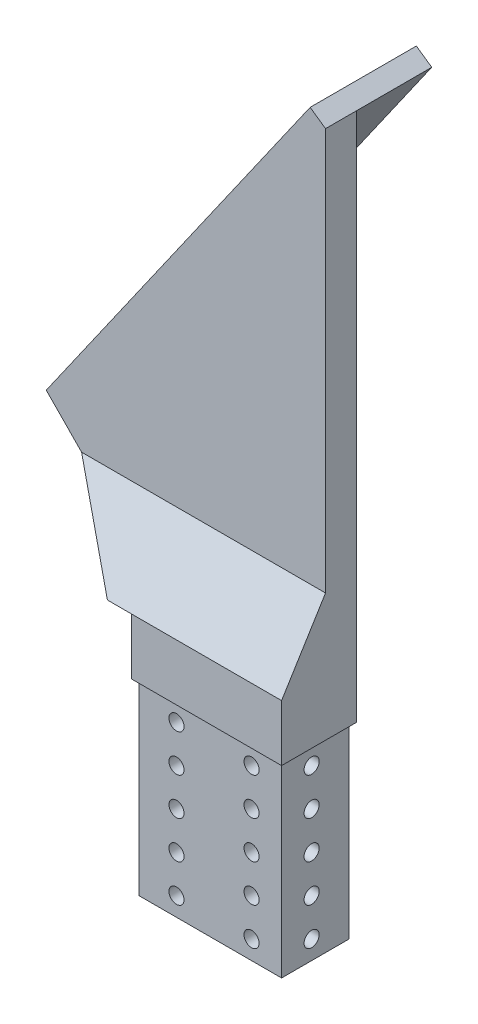
SolidWorks part; units mm, degrees
ref_plane "Front Plane" through (0, 0, 0) normal (0, 0, 1) x (1, 0, 0)
ref_plane "Top Plane" through (0, 0, 0) normal (0, 1, 0) x (1, 0, 0)
ref_plane "Right Plane" through (0, 0, 0) normal (1, 0, 0) x (0, 0, -1)
sketch "Sketch1" plane through (0, 0, 0) normal (0, 0, 1) x (1, 0, 0)
  line L0 (50.8, 82.55) -> (152.4, 82.55)
  line L1 (0, 0) -> (50.8, 0)
  line L2 (0, 0) -> (0, 82.55)
  line L4 (50.8, 0) -> (50.8, 82.55)
  line L5 (-101.6, 82.55) -> (0, 82.55)
  line L6 (-101.6, 82.55) -> (-101.6, 254)
  line L7 (-101.6, 254) -> (152.4, 254)
  line L8 (152.4, 82.55) -> (152.4, 254)
  dimension "D1" = 50.8
  dimension "D2" = 82.55
  dimension "D3" = 254
  dimension "D4" = 171.45
extrude "Boss-Extrude1" add sketch "Sketch1" along normal blind 25.4
sketch "Sketch3" plane through (0, 0, 25.4) normal (0, 0, 1) x (1, 0, 0)
  line L0 (50.8, 0) -> (50.8, 82.55) construction
  line L1 (0, 0) -> (50.8, 0)
  line L2 (0, 0) -> (0, 63.5)
  line L3 (0, 63.5) -> (50.8, 63.5)
  line L4 (50.8, 0) -> (50.8, 63.5)
  dimension "D1" = 63.5
sketch "Sketch4" plane through (0, 0, 0) normal (-1, 0, 0) x (0, 0, 1)
  line L0 (25.4, 0) -> (25.4, 63.5) construction
  line L1 (0, 0) -> (25.4, 0)
  line L2 (0, 0) -> (0, 63.5)
  line L3 (0, 63.5) -> (25.4, 63.5)
  line L4 (25.4, 0) -> (25.4, 63.5)
  dimension "D1" = 63.5
sketch "Sketch5" plane through (0, 0, 0) normal (0, 0, -1) x (-1, 0, 0)
  line L1 (0, 0) -> (-50.8, 0)
  line L2 (0, 0) -> (0, 63.5)
  line L3 (0, 63.5) -> (-50.8, 63.5)
  line L4 (-50.8, 0) -> (-50.8, 63.5)
sketch "Sketch6" plane through (50.8, 0, 0) normal (1, 0, 0) x (0, 0, -1)
  line L1 (0, 0) -> (-25.4, 0)
  line L2 (0, 0) -> (0, 63.5)
  line L3 (0, 63.5) -> (-25.4, 63.5)
  line L4 (-25.4, 0) -> (-25.4, 63.5)
extrude "Cut-Extrude1" cut sketch "Sketch3" against normal blind 1.27
extrude "Cut-Extrude2" cut sketch "Sketch4" against normal blind 1.27
extrude "Cut-Extrude3" cut sketch "Sketch5" against normal blind 1.27
extrude "Cut-Extrude4" cut sketch "Sketch6" against normal blind 1.27
sketch "Sketch7" plane through (0, 0, 25.4) normal (0, 0, 1) x (1, 0, 0)
  line L0 (50.8, 82.55) -> (50.8, 254)
  line L4 (152.4, 254) -> (-101.6, 254) construction
  line L5 (50.8, 82.55) -> (152.4, 82.55)
  line L6 (152.4, 82.55) -> (152.4, 254)
  line L7 (152.4, 254) -> (50.8, 254)
extrude "Cut-Extrude5" cut sketch "Sketch7" against normal through all
sketch "Sketch9" plane through (0, 0, 25.4) normal (0, 0, 1) x (1, 0, 0)
  line L0 (34.6576, 254) -> (50.8, 254)
  line L1 (50.8, 254) -> (-101.6, 254) construction
  line L2 (50.8, 254) -> (50.8, 242.697)
  line L3 (50.8, 242.697) -> (34.6576, 254)
  line L4 (50.8, 63.5) -> (50.8, 254) construction
  dimension "D1" = 11.303
  dimension "D2" = 35
extrude "Cut-Extrude7" cut sketch "Sketch9" against normal through all
sketch "Sketch8" plane through (0, 0, 25.4) normal (0, 0, 1) x (1, 0, 0)
  line L2 (34.6576, 254) -> (-101.6, 254) construction
  line L12 (34.6576, 254) -> (-101.6, 59.4039)
  line L13 (-101.6, 59.4039) -> (-101.6, 254)
  line L14 (-101.6, 254) -> (34.6576, 254)
  dimension "D1" = 55
extrude "Cut-Extrude6" cut sketch "Sketch8" against normal through all
sketch "Sketch10" plane through (0, 0, 25.4) normal (0, 0, 1) x (1, 0, 0)
  line L0 (34.6576, 254) -> (45.5977, 246.3397)
  line L1 (34.6576, 254) -> (50.8, 242.697) construction
  line L2 (45.5977, 246.3397) -> (-84.0298, 61.2124)
  line L4 (-84.0298, 61.2124) -> (-94.9699, 68.8727)
  line L5 (-94.9699, 68.8727) -> (34.6576, 254)
  line L6 (-85.3929, 82.55) -> (34.6576, 254) construction
  dimension "D1" = 13.3553
  dimension "D2" = 13.3553
extrude "Cut-Extrude8" cut sketch "Sketch10" against normal through all
sketch "Sketch11" plane through (0, 0, 24.13) normal (0, 0, 1) x (1, 0, 0)
  line L0 (1.27, 63.5) -> (1.27, 0) construction
  line L1 (50.8, 63.5) -> (0, 63.5) construction
  line L2 (49.53, 63.5) -> (1.27, 63.5) construction
  circle A0 centre (13.97, 57.15) radius 2.5527
  circle A1 centre (13.97, 44.45) radius 2.5527
  circle A2 centre (13.97, 31.75) radius 2.5527
  circle A3 centre (13.97, 19.05) radius 2.5527
  circle A4 centre (13.97, 6.35) radius 2.5527
  circle A5 centre (39.37, 44.45) radius 2.5527
  circle A6 centre (39.37, 31.75) radius 2.5527
  circle A7 centre (39.37, 19.05) radius 2.5527
  circle A8 centre (39.37, 6.35) radius 2.5527
  circle A9 centre (39.37, 57.15) radius 2.5527
  dimension "D1" = 5.1054
  dimension "D2" = 12.7
  dimension "D3" = 6.35
  dimension "D6" = 25.4
  dimension "D7" = 12.7
  dimension "D8" = 6.35
  dimension "D4" = 5
  dimension "D5" = 2
sketch "Sketch12" plane through (1.27, 0, 0) normal (-1, 0, 0) x (0, 0, 1)
  line L0 (0, 63.5) -> (25.4, 63.5) construction
  line L1 (1.27, 0) -> (1.27, 63.5) construction
  circle A0 centre (13.97, 57.15) radius 2.5527
  circle A1 centre (13.97, 44.45) radius 2.5527
  circle A2 centre (13.97, 31.75) radius 2.5527
  circle A3 centre (13.97, 19.05) radius 2.5527
  circle A4 centre (13.97, 6.35) radius 2.5527
  dimension "D1" = 6.35
  dimension "D2" = 12.7
  dimension "D3" = 5.1054
  dimension "D5" = 12.7
  dimension "D4" = 5
extrude "Cut-Extrude9" cut sketch "Sketch11" against normal through all
extrude "Cut-Extrude10" cut sketch "Sketch12" against normal through all
sketch "Sketch17" plane through (0, 0, 0) normal (0, 0, -1) x (-1, 0, 0)
  line L0 (-45.5977, 246.3397) -> (-50.7993, 242.6975)
  line L1 (-45.5977, 246.3397) -> (-50.8, 242.697) construction
  line L2 (-50.7993, 242.6975) -> (68.988, 71.6236)
  line L3 (68.988, 71.6236) -> (74.1896, 75.2658)
  line L4 (74.1896, 75.2658) -> (-45.5977, 246.3397)
  point P5 (0, 0)
  point P8 (0, 0)
  point P9 (0, 0)
  point P10 (0, 0)
  dimension "D1" = 6.35
extrude "Boss-Extrude2" add sketch "Sketch17" along normal blind 25.4
sketch "Sketch18" plane through (0, 0, -25.4) normal (0, 0, -1) x (-1, 0, 0)
  line L0 (61.3372, 82.55) -> (69.0891, 82.55)
  line L1 (69.0891, 82.55) -> (74.1896, 75.2658)
  line L2 (74.1896, 75.2658) -> (68.988, 71.6236)
  line L3 (68.988, 71.6236) -> (61.3372, 82.55)
extrude "Cut-Extrude11" cut sketch "Sketch18" against normal through all
sketch "Sketch19" plane through (0, 0, 25.4) normal (0, 0, 1) x (1, 0, 0)
  line L0 (-8.1291, 82.55) -> (-43.6813, 118.8361)
  line L1 (-69.0891, 82.55) -> (0, 82.55) construction
  line L2 (-69.0891, 82.55) -> (45.5977, 246.3397) construction
  line L3 (-43.6813, 118.8361) -> (-69.0891, 82.55)
  line L4 (-69.0891, 82.55) -> (-8.1291, 82.55)
  dimension "D1" = 50.8
  dimension "D2" = 60.96
extrude "Cut-Extrude12" cut sketch "Sketch19" against normal through all
sketch "Sketch20" plane through (50.8, 0, 0) normal (1, 0, 0) x (0, 0, -1)
  line L0 (-25.4, 82.55) -> (-10.5337, 106.6397)
  line L1 (-25.4, 63.5) -> (-25.4, 242.697) construction
  line L2 (-10.5337, 106.6397) -> (-10.5337, 246.3397)
  line L3 (25.4, 246.3397) -> (-25.4, 246.3397) construction
  line L4 (-10.5337, 246.3397) -> (-25.4, 246.3397)
  line L5 (-25.4, 246.3397) -> (-25.4, 82.55)
  dimension "D1" = 19.05
  dimension "D2" = 139.7
extrude "Cut-Extrude13" cut sketch "Sketch20" against normal through all
